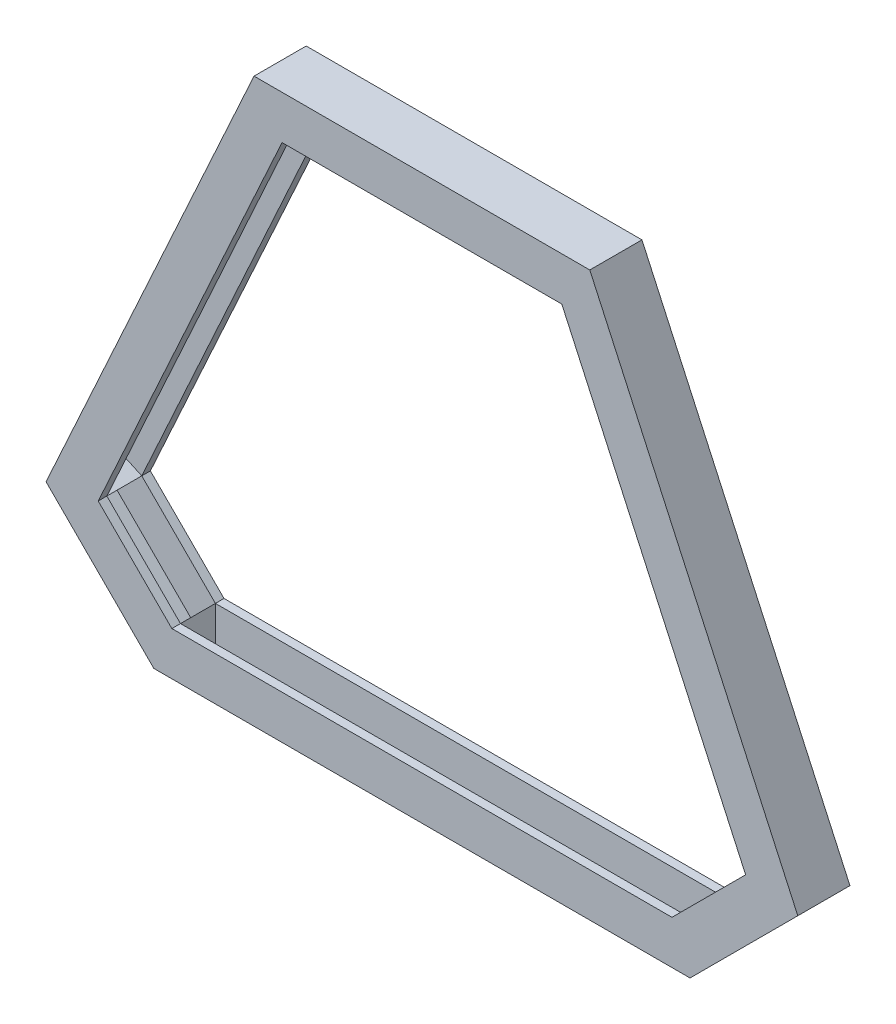
SolidWorks part; units mm, degrees
ref_plane "Front Plane" through (0, 0, 0) normal (0, 0, 1) x (1, 0, 0)
ref_plane "Top Plane" through (0, 0, 0) normal (0, 1, 0) x (1, 0, 0)
ref_plane "Right Plane" through (0, 0, 0) normal (1, 0, 0) x (0, 0, -1)
sketch "Sketch1" plane through (0, 0, 0) normal (0, 0, 1) x (1, 0, 0)
  line L0 (0, -264.5165) -> (-62.614, -327.1305)
  line L1 (-62.614, -327.1305) -> (-374.1336, -327.1305)
  line L2 (-374.1336, -327.1305) -> (-436.7476, -264.5165)
  line L3 (-436.7476, -264.5165) -> (-315.9032, 0)
  line L4 (-315.9032, 0) -> (-120.8445, 0)
  line L5 (-120.8445, 0) -> (0, -264.5165)
extrude "Boss-Extrude1" add sketch "Sketch1" along normal blind 5
sketch "Sketch2" plane through (0, 0, 5) normal (0, 0, 1) x (1, 0, 0)
  line L0 (-315.9032, 0) -> (-436.7476, -264.5165) construction
  line L1 (-436.7476, -264.5165) -> (-374.1336, -327.1305) construction
  line L2 (-374.1336, -327.1305) -> (-62.614, -327.1305) construction
  line L3 (-62.614, -327.1305) -> (0, -264.5165) construction
  line L4 (0, -264.5165) -> (-120.8445, 0) construction
  line L5 (-120.8445, 0) -> (-315.9032, 0) construction
  line L6 (-374.1336, -327.1305) -> (-370.5981, -323.595) construction
  line L7 (-436.7476, -264.5165) -> (-433.2121, -260.981) construction
  line L8 (-315.9032, 0) -> (-311.3553, -2.0777) construction
  line L9 (-436.7476, -264.5165) -> (-432.1998, -266.5942) construction
  line L10 (-315.9032, 0) -> (-315.9032, -5) construction
  line L11 (-120.8445, 0) -> (-120.8445, -5) construction
  line L12 (-120.8445, 0) -> (-125.3924, -2.0777) construction
  line L13 (0, -264.5165) -> (-4.5479, -266.5942) construction
  line L14 (-374.1336, -327.1305) -> (-374.1336, -322.1305) construction
  line L15 (-62.614, -327.1305) -> (-62.614, -322.1305) construction
  line L16 (-62.614, -327.1305) -> (-66.1495, -323.595) construction
  line L17 (0, -264.5165) -> (-3.5355, -260.981) construction
  line L18 (-433.2121, -260.981) -> (-370.5981, -323.595) construction
  line L19 (-374.1336, -322.1305) -> (-62.614, -322.1305) construction
  line L20 (-3.5355, -260.981) -> (-66.1495, -323.595) construction
  line L21 (-125.3924, -2.0777) -> (-4.5479, -266.5942) construction
  line L22 (-120.8445, -5) -> (-315.9032, -5) construction
  line L23 (-311.3553, -2.0777) -> (-432.1998, -266.5942) construction
  line L24 (-311.3553, -2.0777) -> (-292.8909, -10.5132) construction
  line L25 (-315.9032, -5) -> (-315.9032, -25.3) construction
  line L26 (-433.2121, -260.981) -> (-418.8578, -246.6267) construction
  line L27 (-432.1998, -266.5942) -> (-413.7354, -275.0297) construction
  line L28 (-374.1336, -322.1305) -> (-374.1336, -301.8305) construction
  line L29 (-370.5981, -323.595) -> (-356.2438, -309.2407) construction
  line L30 (-66.1495, -323.595) -> (-80.5038, -309.2407) construction
  line L31 (-62.614, -322.1305) -> (-62.614, -301.8305) construction
  line L32 (-4.5479, -266.5942) -> (-23.0122, -275.0297) construction
  line L33 (-3.5355, -260.981) -> (-17.8898, -246.6267) construction
  line L34 (-120.8445, -5) -> (-120.8445, -25.3) construction
  line L35 (-125.3924, -2.0777) -> (-143.8567, -10.5132) construction
  line L36 (-315.9032, -25.3) -> (-120.8445, -25.3) construction
  line L37 (-143.8567, -10.5132) -> (-23.0122, -275.0297) construction
  line L38 (-17.8898, -246.6267) -> (-80.5038, -309.2407) construction
  line L39 (-62.614, -301.8305) -> (-374.1336, -301.8305) construction
  line L40 (-356.2438, -309.2407) -> (-418.8578, -246.6267) construction
  line L41 (-413.7354, -275.0297) -> (-292.8909, -10.5132) construction
  point P17 (0, 0)
sketch "Sketch3" plane through (0, 0, 5) normal (0, 0, 1) x (1, 0, 0)
  line L7 (-137.1013, -25.3) -> (-299.6463, -25.3)
  line L8 (-143.8567, -10.5132) -> (-23.0122, -275.0297) construction
  line L9 (-413.7354, -275.0297) -> (-292.8909, -10.5132) construction
  line L10 (-315.9032, -25.3) -> (-120.8445, -25.3) construction
  line L11 (-137.1013, -25.3) -> (-30.3127, -259.0496)
  line L12 (-17.8898, -246.6267) -> (-80.5038, -309.2407) construction
  line L13 (-30.3127, -259.0496) -> (-73.0936, -301.8305)
  line L14 (-299.6463, -25.3) -> (-406.4349, -259.0496)
  line L15 (-356.2438, -309.2407) -> (-418.8578, -246.6267) construction
  line L16 (-62.614, -301.8305) -> (-374.1336, -301.8305) construction
  line L17 (-406.4349, -259.0496) -> (-363.654, -301.8305)
  line L18 (-73.0936, -301.8305) -> (-363.654, -301.8305)
extrude "Cut-Extrude1" cut sketch "Sketch3" against normal through all
sketch "Sketch4" plane through (0, 0, 5) normal (0, 0, 1) x (1, 0, 0)
  line L0 (-312.6903, -5) -> (-124.0573, -5)
  line L1 (-120.8445, -5) -> (-315.9032, -5) construction
  line L2 (-311.3553, -2.0777) -> (-432.1998, -266.5942) construction
  line L3 (-125.3924, -2.0777) -> (-4.5479, -266.5942) construction
  line L4 (-312.6903, -5) -> (-430.757, -263.4361)
  line L5 (-433.2121, -260.981) -> (-370.5981, -323.595) construction
  line L6 (-430.757, -263.4361) -> (-372.0626, -322.1305)
  line L11 (-374.1336, -322.1305) -> (-62.614, -322.1305) construction
  line L12 (-372.0626, -322.1305) -> (-64.6851, -322.1305)
  line L13 (-3.5355, -260.981) -> (-66.1495, -323.595) construction
  line L14 (-64.6851, -322.1305) -> (-5.9907, -263.4361)
  line L15 (-5.9907, -263.4361) -> (-124.0573, -5)
  line L16 (-315.9032, 0) -> (-120.8445, 0)
  line L17 (-315.9032, 0) -> (-436.7476, -264.5165)
  line L18 (-436.7476, -264.5165) -> (-374.1336, -327.1305)
  line L19 (-374.1336, -327.1305) -> (-62.614, -327.1305)
  line L20 (-62.614, -327.1305) -> (0, -264.5165)
  line L21 (0, -264.5165) -> (-120.8445, 0)
extrude "Boss-Extrude3" add sketch "Sketch4" along normal blind 20.3
sketch "Sketch5" plane through (0, 0, 5) normal (0, 0, 1) x (1, 0, 0)
  line L0 (-299.6463, -25.3) -> (-318.1107, -16.8645)
  line L1 (-312.6903, -5) -> (-430.757, -263.4361) construction
  line L2 (-299.6463, -25.3) -> (-299.6463, -5)
  line L3 (-124.0573, -5) -> (-312.6903, -5) construction
  line L4 (-137.1013, -25.3) -> (-137.1013, -5)
  line L5 (-137.1013, -25.3) -> (-118.637, -16.8645)
  line L6 (-5.9907, -263.4361) -> (-124.0573, -5) construction
  line L7 (-406.4349, -259.0496) -> (-424.8993, -250.6142)
  line L8 (-406.4349, -259.0496) -> (-420.7892, -273.4039)
  line L9 (-430.757, -263.4361) -> (-372.0626, -322.1305) construction
  line L10 (-363.654, -301.8305) -> (-378.0083, -316.1848)
  line L11 (-363.654, -301.8305) -> (-363.654, -322.1305)
  line L12 (-372.0626, -322.1305) -> (-64.6851, -322.1305) construction
  line L13 (-372.0626, -322.1305) -> (-64.6851, -322.1305) construction
  line L14 (-73.0936, -301.8305) -> (-73.0936, -322.1305)
  line L15 (-73.0936, -301.8305) -> (-58.7393, -316.1848)
  line L16 (-64.6851, -322.1305) -> (-5.9907, -263.4361) construction
  line L17 (-30.3127, -259.0496) -> (-15.9585, -273.4039)
  line L18 (-30.3127, -259.0496) -> (-11.8484, -250.6142)
  line L19 (-312.6903, -5) -> (-318.1107, -16.8645)
  line L20 (-312.6903, -5) -> (-299.6463, -5)
  line L21 (-137.1013, -5) -> (-124.0573, -5)
  line L22 (-124.0573, -5) -> (-118.637, -16.8645)
  line L23 (-424.8993, -250.6142) -> (-430.757, -263.4361)
  line L24 (-430.757, -263.4361) -> (-420.7892, -273.4039)
  line L25 (-378.0083, -316.1848) -> (-372.0626, -322.1305)
  line L26 (-372.0626, -322.1305) -> (-363.654, -322.1305)
  line L27 (-73.0936, -322.1305) -> (-64.6851, -322.1305)
  line L28 (-58.7393, -316.1848) -> (-64.6851, -322.1305)
  line L29 (-11.8484, -250.6142) -> (-5.9907, -263.4361)
  line L30 (-5.9907, -263.4361) -> (-15.9585, -273.4039)
extrude "Boss-Extrude4" add sketch "Sketch5" along normal up to surface (20.3 mm away) up to face at (-218.3738, -197.2157, 25.3)
sketch "Sketch6" plane through (0, 0, 25.3) normal (0, 0, 1) x (1, 0, 0)
  line L0 (-315.9032, 0) -> (-120.8445, 0)
  line L1 (-120.8445, 0) -> (0, -264.5165)
  line L2 (0, -264.5165) -> (-62.614, -327.1305)
  line L3 (-62.614, -327.1305) -> (-374.1336, -327.1305)
  line L4 (-374.1336, -327.1305) -> (-436.7476, -264.5165)
  line L5 (-436.7476, -264.5165) -> (-315.9032, 0)
  line L6 (-299.6463, -25.3) -> (-406.4349, -259.0496)
  line L7 (-406.4349, -259.0496) -> (-363.654, -301.8305)
  line L8 (-406.4349, -259.0496) -> (-363.654, -301.8305) construction
  line L9 (-363.654, -301.8305) -> (-378.0083, -316.1848) construction
  line L10 (-363.654, -301.8305) -> (-73.0936, -301.8305)
  line L11 (-73.0936, -301.8305) -> (-30.3127, -259.0496)
  line L12 (-30.3127, -259.0496) -> (-137.1013, -25.3)
  line L13 (-137.1013, -25.3) -> (-299.6463, -25.3)
extrude "Boss-Extrude5" add sketch "Sketch6" along normal blind 5
